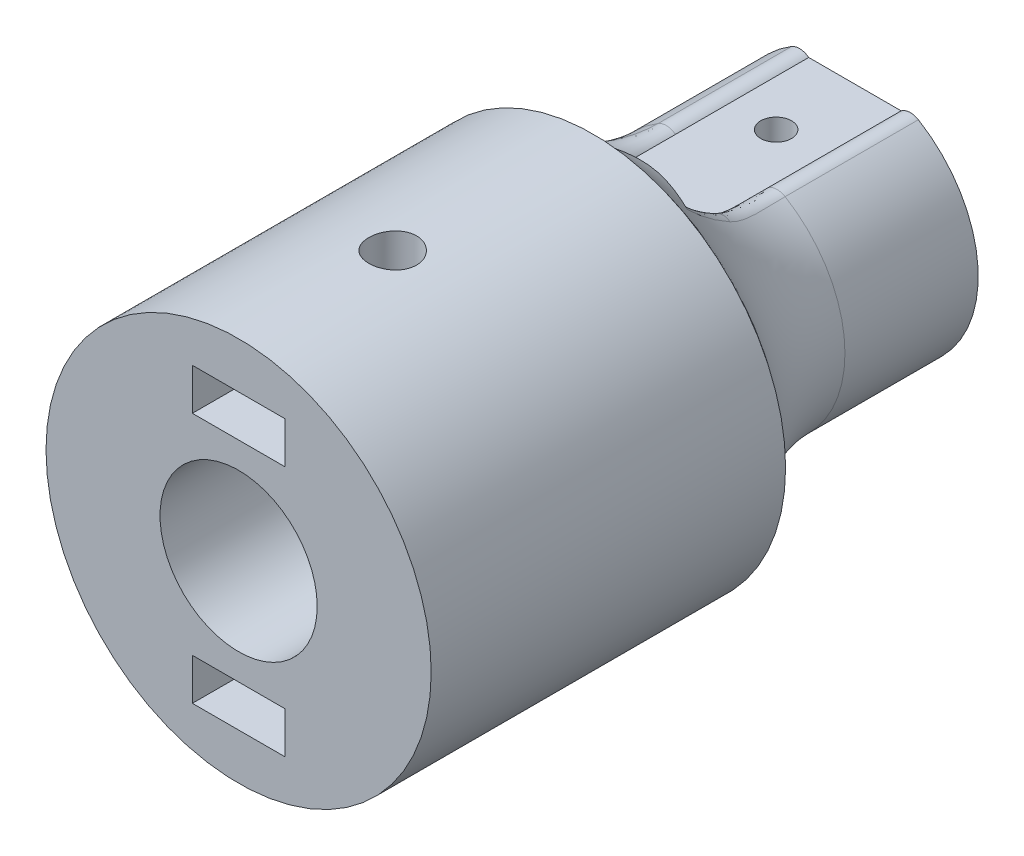
SolidWorks part; units mm, degrees
ref_plane "Ön Düzlem" through (0, 0, 0) normal (0, 0, 1) x (1, 0, 0)
ref_plane "Üst Düzlem" through (0, 0, 0) normal (0, 1, 0) x (1, 0, 0)
ref_plane "Sağ Düzlem" through (0, 0, 0) normal (1, 0, 0) x (0, 0, -1)
sketch "Çizim1" plane through (0, 0, 0) normal (0, 0, 1) x (1, 0, 0)
  circle A0 centre (0, 0) radius 3.85
  circle A1 centre (0, 0) radius 8
  dimension "D1" = 7.7
  dimension "D2" = 16
extrude "Yükseklik-Ekstrüzyon1" add sketch "Çizim1" along normal blind 17
sketch "Çizim2" plane through (0, 0, 17) normal (0, 0, 1) x (1, 0, 0)
  circle A0 centre (0, 0) radius 5.1
  circle A1 centre (0, 0) radius 12.5
  dimension "D1" = 10.2
  dimension "D2" = 25
extrude "Yükseklik-Ekstrüzyon2" add sketch "Çizim2" along normal blind 23
fillet "Radyus1" radius 10 1 edges at (8, 0, 17)
sketch "Çizim3" plane through (0, 0, 40) normal (0, 0, 1) x (1, 0, 0)
  line L2 (0, -9.5) -> (3, -9.5)
  line L3 (0, 9.5) -> (3, 9.5)
  line L5 (3, -9.5) -> (-3, -9.5)
  line L6 (3, -9.5) -> (3, -6.8)
  line L7 (3, -6.8) -> (-3, -6.8)
  line L8 (-3, -9.5) -> (-3, -6.8)
  line L9 (3, 9.5) -> (-3, 9.5)
  line L10 (3, 9.5) -> (3, 6.8)
  line L11 (3, 6.8) -> (-3, 6.8)
  line L12 (-3, 9.5) -> (-3, 6.8)
  dimension "D1" = 9.5
  dimension "D2" = 19
  dimension "D3" = 3
  dimension "D4" = 2.7
  dimension "D5" = 2.7
  dimension "D6" = 6
  dimension "D7" = 6
  dimension "D8" = 3
extrude "Kes-Ekstrüzyon2" cut sketch "Çizim3" against normal blind 50 contours L9 L12 L11 L10 L3 | L8 L5 L2 L6 L7
fillet "Radyus2" radius 1 8 edges at (3, 7.4162, 4.3242) (-3, 7.4162, 4.3242) (-3, -7.4162, 4.3242) (3, -7.7209, 11.0117) (3, 7.7209, 11.0117) (-3, 7.7209, 11.0117) (-3, -7.7209, 11.0117) (3, -7.4162, 4.3242)
sketch "Çizim4" plane through (0, 0, 0) normal (0, 1, 0) x (1, 0, 0)
  line L0 (-12.5, -40) -> (12.5, -40) construction
  circle A0 centre (0, -5.1146) radius 1
  circle A1 centre (0, -30) radius 1.55
  dimension "D1" = 2
  dimension "D2" = 3.1
  dimension "D3" = 10
extrude "Kes-Ekstrüzyon4" cut sketch "Çizim4" against normal blind 32 and the other way blind 26
